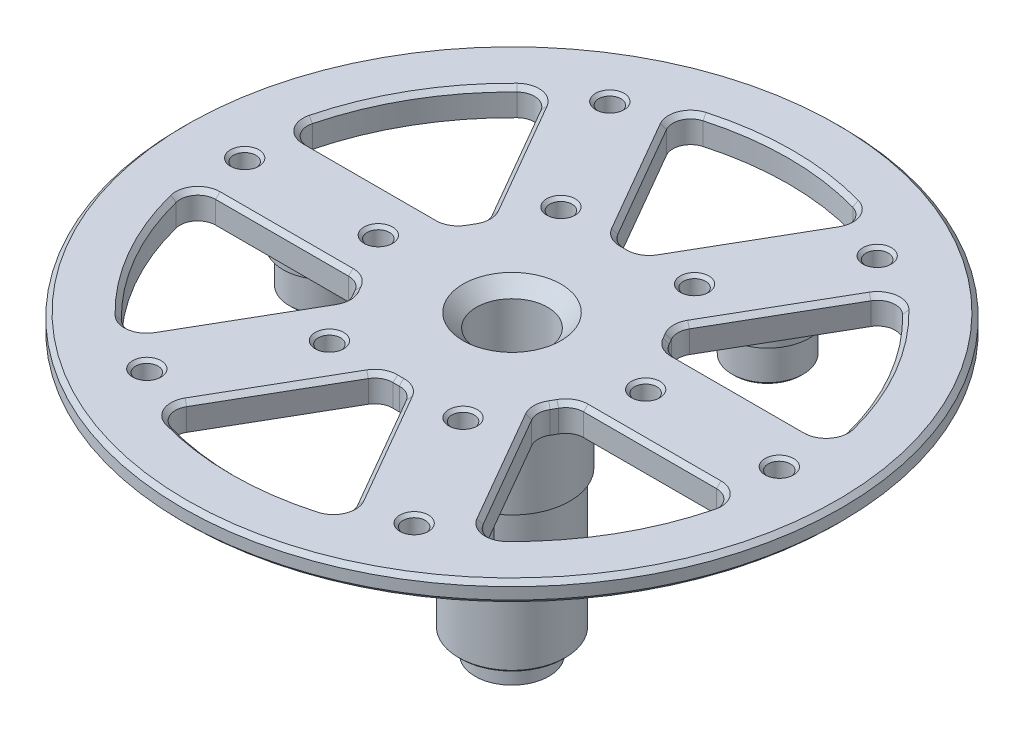
SolidWorks part; units mm, degrees
ref_plane "Front Plane" through (0, 0, 0) normal (0, 0, 1) x (1, 0, 0)
ref_plane "Top Plane" through (0, 0, 0) normal (0, 1, 0) x (1, 0, 0)
ref_plane "Right Plane" through (0, 0, 0) normal (1, 0, 0) x (0, 0, -1)
ref_axis "Axis1" through (0, 0, 0) along (0, 1, 0)
sketch "Sketch1" plane through (0, 0, 0) normal (0, 0, 1) x (1, 0, 0)
  line L0 (0, 0) -> (0, -6072.8457) construction
  line L2 (-3.15, -8.7) -> (-4, -8.7)
  line L3 (-4, -8.7) -> (-4, 19.6)
  line L4 (-4, 19.6) -> (-5.5, 21.1)
  line L5 (-5.5, 21.1) -> (-37, 21.1)
  line L6 (-32, 18.8) -> (-32, 18.1)
  line L7 (-32, 18.1) -> (-6.5, 18.1)
  line L8 (-6.5, 18.1) -> (-6.5, 6)
  line L9 (-6.5, 6) -> (-6, 6)
  line L10 (-6, 6) -> (-6, 5.15)
  line L13 (-33.5, 36.8027) -> (-33.5, 11.6549) construction
  line L14 (-6, -6) -> (-6, -7.1)
  line L15 (6.5, -9.7) -> (-6.5, -9.7) construction
  line L18 (-6, -9.7) -> (-4.15, -9.7)
  line L20 (-32, 18.8) -> (-37, 18.8)
  line L21 (36.5, 17.8) -> (-36.5, 17.8) construction
  line L24 (-3.15, -12.2) -> (-3.15, -8.7)
  line L25 (-6, -7.1) -> (-6, -9.7)
  line L26 (8.5, 17.1) -> (-8.5, 17.1) construction
  line L27 (-4.15, -9.7) -> (-4.15, -12.2)
  line L28 (-4.15, -12.2) -> (-3.15, -12.2)
  line L29 (-6, -7.1) -> (-5.7, -7.1) construction
  line L31 (-6, -6) -> (-5.7, -6) construction
  line L32 (-5.7, -7.1) -> (-5.7, -6) construction
  line L33 (-37, 18.8) -> (-37, 21.1)
  line L34 (-33, 17.1) -> (-33, 17.8) construction
  line L35 (-37, 17.3) -> (-37, 6) construction
  line L47 (-6, 5.15) -> (-6, -6)
  line L49 (6.25, 6) -> (-6.25, 6) construction
  line L50 (-6.25, -6) -> (6.25, -6) construction
  dimension "D1" = 8
  dimension "D2" = 3
  dimension "D3" = 1
  dimension "D4" = 12
  dimension "D5" = 135
  dimension "D6" = 1.5
  dimension "D7" = 1
  dimension "D8" = 8.3
  dimension "D9" = 13
  dimension "D10" = 0.3
  dimension "D11" = 1.1
  dimension "D13" = 2.5
  dimension "D14" = 1
  dimension "D15" = 33.5
  dimension "D16" = 1
  dimension "D17" = 1
revolve "Revolve1" add sketch "Sketch1" angle 360 about L0
chamfer "Chamfer1" distance 0.5 angle 45 1 edges at (0, -12.2, 3.15)
sketch "Sketch2" plane through (0, 0, 0) normal (0, 0, 1) x (1, 0, 0)
  line L0 (0, 0) -> (0, 50000) construction
  line L1 (-21, 33.1641) -> (-21, -6.3072) construction
  line L2 (-21, 18.1) -> (-25.7, 18.1)
  line L3 (-32, 18.1) -> (32, 18.1) construction
  line L4 (-32, 18.1) -> (-6.5, 18.1) construction
  line L5 (-25.7, 18.1) -> (-25.7, 17.1)
  line L6 (-25.7, 17.1) -> (-25, 17.1)
  line L7 (-25, 17.1) -> (-25, 13)
  line L8 (-25, 13) -> (-21, 13)
  line L9 (-21, 13) -> (-21, 18.1)
  dimension "D1" = 21
  dimension "D2" = 8
  dimension "D3" = 0.7
  dimension "D4" = 4.1
  dimension "D5" = 1
revolve "Planet bearing axis" add sketch "Sketch2" angle 360 about L1
chamfer "Chamfer2" distance 0.25 angle 45 1 edges at (-25, 13, 0)
pattern_circular "CirPattern1" count 3 over 360 about axis through (0, 0, 0) along (0, 1, 0) of "Planet bearing axis", "Chamfer2"
chamfer "Chamfer3" distance 0.25 angle 45 1 edges at (0, -9.7, 6)
chamfer "Chamfer4" distance 0.5 angle 45 3 edges at (0, 21.1, 37) (0, 18.8, 37) (0, 18.1, 6.5)
hole_wizard "M3x0.5 Tapped Hole1" positions "Sketch3" profile "Sketch4" tap size "M3x0.5" standard "ANSI Metric" end condition through all
sketch "Sketch3" plane through (0, 21.1, 0) normal (0, 1, 0) x (1, 0, 0)
  circle A2 centre (0, 0) radius 30 construction
  point P0 (-30, 0)
  dimension "D1" = 60
sketch "Sketch4" plane through (-30, 21.1, 0) normal (1, 0, 0) x (0, 0, 1)
  line L0 (0, 0) -> (0, 33.3)
  line L1 (0, 33.3) -> (1.25, 33.3)
  line L2 (1.25, 33.3) -> (1.25, 0.35)
  line L3 (1.25, 0.35) -> (1.6, 0)
  line L5 (1.6, 0) -> (0, 0)
  line L6 (-1.25, 0.35) -> (-1.6, 0) construction
  line L11 (0, -6.35) -> (0, 107.95) construction
  dimension "Thru Tap Drill Dia." = 2.5
  dimension "Thru Tap Drill Depth" = 33.3
  dimension "Near C'Sink Dia." = 3.2
  dimension "Near C'Sink Angle" = 90
cosmetic thread "Hole Thread1" parameters "D2"=3
hole_wizard "M3x0.5 Tapped Hole2" positions "Sketch5" profile "Sketch6" tap size "M3x0.5" standard "ANSI Metric" end condition through all
sketch "Sketch5" plane through (0, 21.1, 0) normal (0, 1, 0) x (1, 0, 0)
  circle A0 centre (0, 0) radius 15 construction
  point P0 (-15, 0)
  dimension "D1" = 30
sketch "Sketch6" plane through (-15, 21.1, 0) normal (1, 0, 0) x (0, 0, 1)
  line L0 (0, 0) -> (0, 33.3)
  line L1 (0, 33.3) -> (1.25, 33.3)
  line L2 (1.25, 33.3) -> (1.25, 0.35)
  line L3 (1.25, 0.35) -> (1.6, 0)
  line L5 (1.6, 0) -> (0, 0)
  line L6 (-1.25, 0.35) -> (-1.6, 0) construction
  line L11 (0, -6.35) -> (0, 107.95) construction
  dimension "Thru Tap Drill Dia." = 2.5
  dimension "Thru Tap Drill Depth" = 33.3
  dimension "Near C'Sink Dia." = 3.2
  dimension "Near C'Sink Angle" = 90
cosmetic thread "Hole Thread2" parameters "D2"=3
pattern_circular "CirPattern2" count 6 over 360 about axis through (0, 0, 0) along (0, 1, 0) of "M3x0.5 Tapped Hole1", "M3x0.5 Tapped Hole2"
sketch "Sketch7" plane through (0, 0, 0) normal (0, 1, 0) x (1, 0, 0)
  line L0 (0, 0) -> (-50000, 0) construction
  line L1 (0, 0) -> (-37.8615, -21.8593) construction
  line L2 (-19.7451, -23.8983) -> (-10.4286, -7.7617)
  line L3 (-11.9361, -5.1506) -> (-30.5691, -5.1506)
  arc A0 (-30.5691, -5.1506) -> (-19.7451, -23.8983) centre (0, 0) ccw
  arc A1 (-11.9361, -5.1506) -> (-10.4286, -7.7617) centre (0, 0) ccw
  point P11 (-26.8468, -15.5)
  point P12 (-11.2583, -6.5)
  dimension "D3" = 13
  dimension "D4" = 31
  dimension "D1" = 30
  dimension "D2" = 60
extrude "Cut-Extrude1" cut sketch "Sketch7" along normal through all
fillet "Fillet1" radius 2 4 edges at (-19.7451, 19.6, 23.8983) (-30.5691, 19.6, 5.1506) (-10.4286, 19.6, 7.7617) (-11.9361, 19.6, 5.1506)
chamfer "Chamfer5" distance 0.5 angle 45 8 edges at (-14.7832, 21.1, 15.304) (-10.7858, 21.1, 7.8173) (-19.9713, 21.1, 22.7452) (-11.2583, 21.1, 6.5) (-26.8468, 21.1, 15.5) (-12.1629, 21.1, 5.4321) (-29.6836, 21.1, 5.9231) (-20.6453, 21.1, 5.1506)
pattern_circular "CirPattern3" count 6 over 360 about axis through (0, 0, 0) along (0, 1, 0) of "Cut-Extrude1", "Fillet1", "Chamfer5"
